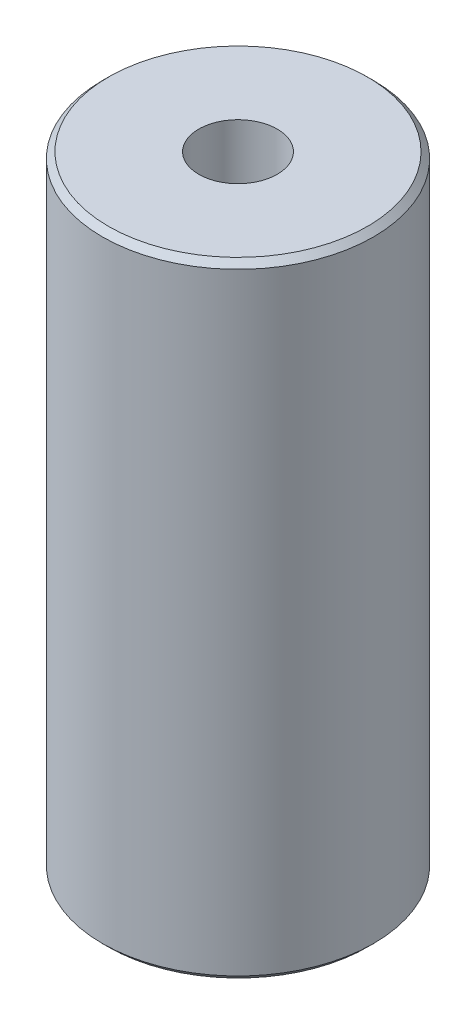
SolidWorks part; units mm, degrees
ref_plane "Front Plane" through (0, 0, 0) normal (0, 0, 1) x (1, 0, 0)
ref_plane "Top Plane" through (0, 0, 0) normal (0, 1, 0) x (1, 0, 0)
ref_plane "Right Plane" through (0, 0, 0) normal (1, 0, 0) x (0, 0, -1)
sketch "Sketch1" plane through (0, 0, 0) normal (0, 1, 0) x (1, 0, 0)
  circle A0 centre (0, 0) radius 55
  dimension "SHAFT_OD" = 110
extrude "Boss-Extrude1" add sketch "Sketch1" along normal blind 253.2954
sketch "Sketch2" plane through (0, 0, 0) normal (0, 1, 0) x (1, 0, 0)
  circle A0 centre (0, 0) radius 15.9276
  dimension "BORE_D" = 31.8552
extrude "Cut-Extrude1" cut sketch "Sketch2" along normal through all
chamfer "Chamfer1" distance 2.4648 angle 45 2 edges at (0, 253.2954, 55) (0, 0, 55)
